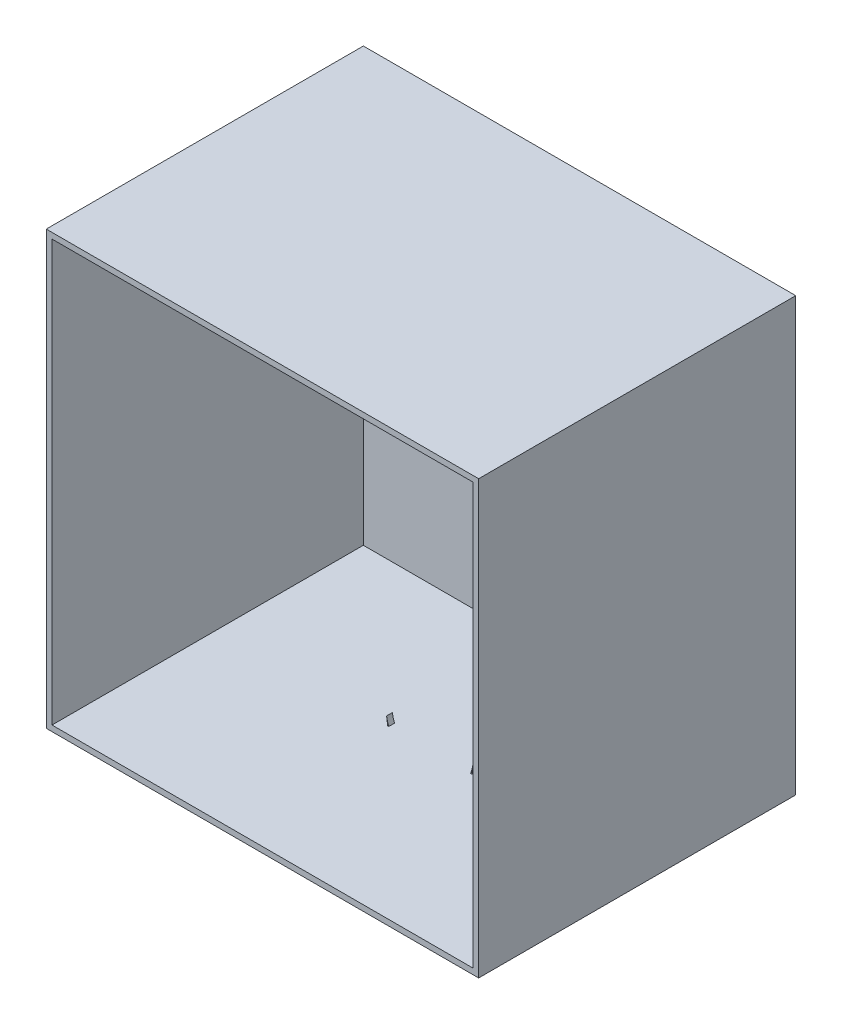
SolidWorks part; units mm, degrees
ref_plane "前视基准面" through (0, 0, 0) normal (0, 0, 1) x (1, 0, 0)
ref_plane "上视基准面" through (0, 0, 0) normal (0, 1, 0) x (1, 0, 0)
ref_plane "右视基准面" through (0, 0, 0) normal (1, 0, 0) x (0, 0, -1)
sketch "草图1" plane through (0, 0, 0) normal (0, 0, 1) x (1, 0, 0)
  line L1 (-75, 75) -> (75, 75)
  line L2 (-75, 75) -> (-75, -75)
  line L3 (-75, -75) -> (75, -75)
  line L4 (75, 75) -> (75, -75)
  line L5 (-75, 75) -> (75, -75) construction
  line L6 (-75, -75) -> (75, 75) construction
  point P0 (0, 0)
  dimension "D1" = 150
extrude "凸台-拉伸1" add sketch "草图1" along normal blind 110
shell "抽壳1" thickness 2 removed face at (0, 0, 110)
sketch "草图2" plane through (0, 0, 110) normal (0, 0, 1) x (1, 0, 0)
  line L0 (-19.9447, -75) -> (-17.3016, -78.9071)
  line L2 (-75, -75) -> (75, -75) construction
  line L11 (0, -75) -> (0, -89.9819) construction
  line L12 (-8.0716, -83.259) -> (0, -82.4909)
  line L13 (-19.9447, -75) -> (-14.3143, -75)
  line L14 (-14.3143, -75) -> (-14.9326, -70.2145)
  line L15 (-5.0151, -78.9331) -> (5.0151, -78.9331)
  line L16 (14.3143, -75) -> (14.9326, -70.2145)
  line L17 (19.9447, -75) -> (14.3143, -75)
  line L18 (8.0716, -83.259) -> (0, -82.4909)
  line L19 (19.9447, -75) -> (17.3016, -78.9071)
  arc A4 (8.0716, -83.259) -> (17.3016, -78.9071) centre (9.0188, -73.3039) ccw
  arc A5 (5.0151, -78.9331) -> (14.9326, -70.2145) centre (5.0151, -68.9331) ccw
  arc A6 (-17.3016, -78.9071) -> (-8.0716, -83.259) centre (-9.0188, -73.3039) ccw
  arc A7 (-14.9326, -70.2145) -> (-5.0151, -78.9331) centre (-5.0151, -68.9331) ccw
  point P12 (0, -78.9331)
  point P17 (13.9775, -83.8209)
  point P20 (13.8062, -78.9331)
  point P23 (-13.9775, -83.8209)
  point P26 (-13.8062, -78.9331)
  dimension "D1" = 10
extrude "凸台-拉伸2" add sketch "草图2" along normal blind 2 from offset 60 offset against normal yes
fillet "圆角1" radius 10 2 edges at (19.9447, -75, 51) (-19.9447, -75, 51)
